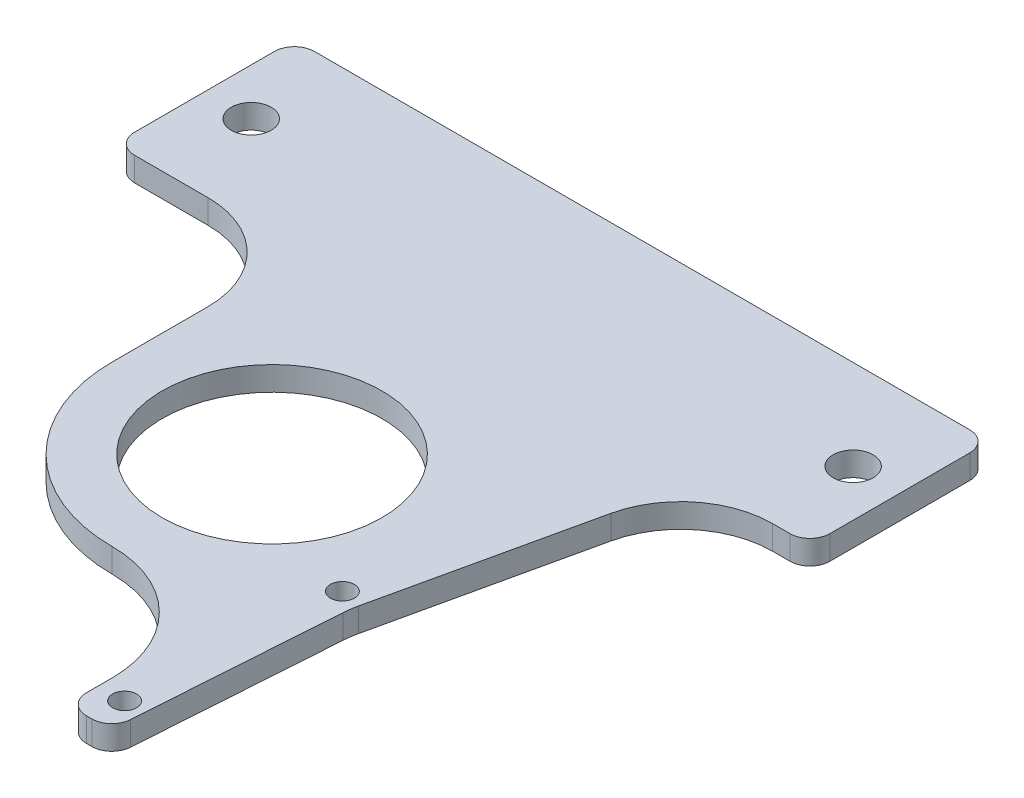
SolidWorks part; units mm, degrees
ref_plane "Front Plane" through (0, 0, 0) normal (0, 0, 1) x (1, 0, 0)
ref_plane "Top Plane" through (0, 0, 0) normal (0, 1, 0) x (1, 0, 0)
ref_plane "Right Plane" through (0, 0, 0) normal (1, 0, 0) x (0, 0, -1)
sketch "Sketch1" plane through (0, 0, 0) normal (0, 1, 0) x (1, 0, 0)
  line L10 (-87, 92.6) -> (87, 92.6)
  line L11 (77.8333, 47.6) -> (30.5, 47.6) construction
  line L12 (87, 50.6) -> (87, 63.8) construction
  line L13 (87, 92.6) -> (87, 47.6)
  line L14 (-87, 92.6) -> (-87, 47.6)
  line L15 (35, -71.9) -> (38.5, -20.9) construction
  line L16 (39.7824, -75.2423) -> (43.1965, -25.4933)
  line L17 (87, 47.6) -> (77.6499, 47.6)
  line L18 (55.2, 29.6) -> (43.6926, -22.068)
  line L19 (39.9883, -72.2423) -> (43.4883, -21.2423) construction
  line L20 (-70.8757, 92.6) -> (-84, 92.6) construction
  line L21 (34.7941, -79.9) -> (33.4627, -79.9)
  line L23 (-63.6246, 47.6) -> (-87, 47.6)
  line L24 (-40, 0) -> (-40, 23.9754)
  line L25 (28.4627, -74.9) -> (28.4627, -68.4627)
  line L26 (-75.3123, 47.6) -> (-75.3123, 92.6) construction
  line L27 (0, -3.3) -> (0, 3.3) construction
  line L28 (75.3123, 47.6) -> (75.3123, 92.6) construction
  line L29 (-63.6246, 47.6) -> (-63.6246, -112.4) construction
  line L30 (-30.5, 47.6) -> (-75, 47.6) construction
  line L31 (-87, 63.8) -> (-87, 50.6) construction
  line L32 (65, 29.6) -> (45.4, 29.6) construction
  circle A0 centre (0, 0) radius 27.5
  circle A1 centre (38.5, -20.9) radius 3
  circle A2 centre (35, -71.9) radius 3
  arc A3 (-40, 0) -> (0, -40) centre (0, 0) ccw
  arc A4 (-40, 23.9754) -> (-63.6246, 47.6) centre (-63.6246, 23.9754) ccw
  arc A5 (0, -40) -> (28.4627, -68.4627) centre (0, -68.4627) cw
  arc A6 (77.6499, 47.6) -> (55.2, 29.6) centre (77.6499, 24.6) ccw
  arc A7 (43.1965, -25.4933) -> (43.6926, -22.068) centre (66.1426, -27.068) cw
  arc A8 (33.4627, -79.9) -> (28.4627, -74.9) centre (33.4627, -74.9) cw
  arc A9 (34.7941, -79.9) -> (39.7824, -75.2423) centre (34.7941, -74.9) ccw
  circle A10 centre (-75.3123, 70.1) radius 5
  circle A11 centre (75.3123, 70.1) radius 5
  point P38 (59.2089, 47.6)
  point P44 (28.4627, -79.9)
  point P47 (39.4627, -79.9)
  point P54 (-87, 70.1)
  dimension "D1" = 55
  dimension "D3" = 80
  dimension "D5" = 23
  dimension "D8" = 5
  dimension "D9" = 6
  dimension "D10" = 10
  dimension "D4" = 11
  dimension "D6" = 8
  dimension "D2" = 5
extrude "Boss-Extrude1" add sketch "Sketch1" along normal blind 6
fillet "Fillet1" radius 5 4 edges at (87, 3, -47.6) (87, 3, -92.6) (-87, 3, -92.6) (-87, 3, -47.6)
